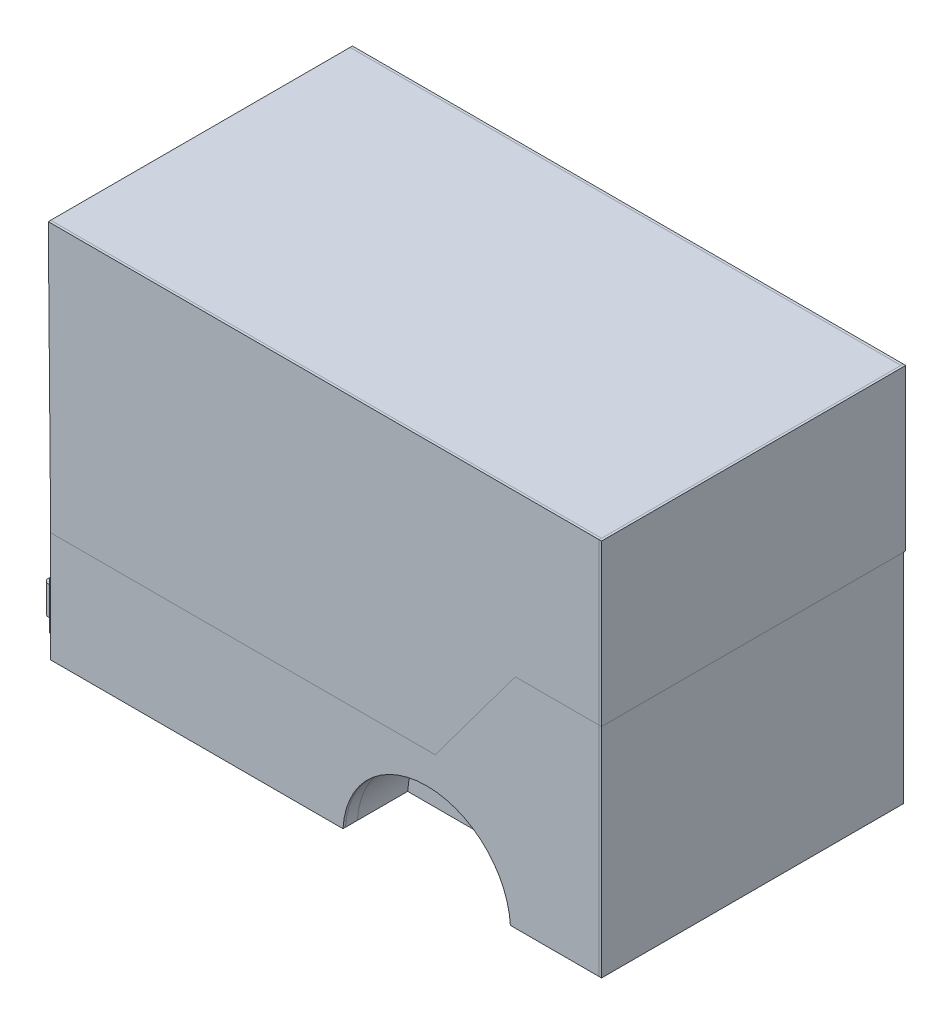
SolidWorks part; units mm, degrees
other "베이스 모듈"
other "결합장치1"
other "측벽"
other "결합장치2"
other "뒷벽인테리어(하양)"
other "뒷벽인테리어(검정)"
other "측벽인테리어(하양)2"
other "측벽인테리어(검정)2"
other "측벽인테리어(검정)1"
other "측벽인테리어(하양)1"
other "뒷벽"
other "천장"
other "뒷면벽"
other "측면벽"
ref_plane "정면" through (0, 0, 0) normal (0, 0, 1) x (1, 0, 0)
ref_plane "윗면" through (0, 0, 0) normal (0, 1, 0) x (1, 0, 0)
ref_plane "우측면" through (0, 0, 0) normal (1, 0, 0) x (0, 0, -1)
sketch "스케치1" plane through (0, 0, 0) normal (0, 1, 0) x (1, 0, 0)
  line L1 (-757.2313, -2.0205) -> (-986.2313, -2.0205)
  line L2 (-757.2313, -2.0205) -> (-757.2313, -127.0205)
  line L3 (-757.2313, -127.0205) -> (-986.2313, -127.0205)
  line L4 (-986.2313, -2.0205) -> (-986.2313, -127.0205)
extrude "보스-돌출1" add sketch "스케치1" along normal up to surface (88 mm away)
sketch "스케치4" plane through (-986.2313, 0, 0) normal (-1, 0, 0) x (0, 0, 1)
  line L4 (2.0205, 0) -> (127.0205, 0)
  line L5 (2.0205, 88) -> (2.0205, 0)
  line L6 (127.0205, 88) -> (2.0205, 88)
  line L7 (127.0205, 0) -> (127.0205, 88)
  line L8 (123.0205, 84) -> (6.0205, 84)
  line L9 (123.0205, 67.306) -> (123.0205, 84)
  line L10 (120.1014, 42.8854) -> (120.8975, 46.7066)
  line L11 (118.0205, 2) -> (118.0205, 22.694)
  line L12 (11.0205, 2) -> (118.0205, 2)
  line L13 (11.0205, 22.694) -> (11.0205, 2)
  line L14 (8.1434, 46.7066) -> (8.9395, 42.8854)
  line L15 (6.0205, 84) -> (6.0205, 67.306)
  line L16 (123.0205, 84) -> (6.0205, 84)
  line L17 (123.0205, 67.306) -> (123.0205, 84)
  line L18 (120.1014, 42.8854) -> (120.8975, 46.7066)
  line L19 (118.0205, 2) -> (118.0205, 22.694)
  line L20 (11.0205, 2) -> (118.0205, 2)
  line L21 (11.0205, 22.694) -> (11.0205, 2)
  line L22 (8.1434, 46.7066) -> (8.9395, 42.8854)
  line L23 (6.0205, 84) -> (6.0205, 67.306)
  line L24 (117.0205, 3) -> (117.0205, 22.694)
  line L25 (119.1224, 43.0894) -> (119.9185, 46.9106)
  line L26 (122.0205, 67.306) -> (122.0205, 83)
  line L27 (122.0205, 83) -> (7.0205, 83)
  line L28 (7.0205, 83) -> (7.0205, 67.306)
  line L29 (9.1224, 46.9106) -> (9.9185, 43.0894)
  line L30 (12.0205, 22.694) -> (12.0205, 3)
  line L31 (12.0205, 3) -> (117.0205, 3)
  line L32 (117.0205, 3) -> (117.0205, 22.694)
  line L33 (119.1224, 43.0894) -> (119.9185, 46.9106)
  line L34 (122.0205, 67.306) -> (122.0205, 83)
  line L35 (122.0205, 83) -> (7.0205, 83)
  line L36 (7.0205, 83) -> (7.0205, 67.306)
  line L37 (9.1224, 46.9106) -> (9.9185, 43.0894)
  line L38 (12.0205, 22.694) -> (12.0205, 3)
  line L39 (12.0205, 3) -> (117.0205, 3)
  line L40 (2.0205, 0) -> (127.0205, 0)
  line L41 (2.0205, 88) -> (2.0205, 0)
  line L42 (127.0205, 88) -> (2.0205, 88)
  line L43 (127.0205, 0) -> (127.0205, 88)
  line L44 (126.0205, 1) -> (126.0205, 87)
  line L45 (3.0205, 1) -> (126.0205, 1)
  line L46 (3.0205, 87) -> (3.0205, 1)
  line L47 (126.0205, 87) -> (3.0205, 87)
  line L48 (126.0205, 1) -> (126.0205, 87)
  line L49 (3.0205, 1) -> (126.0205, 1)
  line L50 (3.0205, 87) -> (3.0205, 1)
  line L51 (126.0205, 87) -> (3.0205, 87)
  arc A200 (120.8975, 46.7066) -> (123.0205, 67.306) centre (22.0205, 67.306) ccw
  arc A202 (120.8975, 46.7066) -> (123.0205, 67.306) centre (22.0205, 67.306) ccw
  arc A204 (120.1014, 42.8854) -> (118.0205, 22.694) centre (217.0205, 22.694) ccw
  arc A206 (120.1014, 42.8854) -> (118.0205, 22.694) centre (217.0205, 22.694) ccw
  arc A208 (11.0205, 22.694) -> (8.9395, 42.8854) centre (-87.9795, 22.694) ccw
  arc A209 (11.0205, 22.694) -> (8.9395, 42.8854) centre (-87.9795, 22.694) ccw
  arc A210 (6.0205, 67.306) -> (8.1434, 46.7066) centre (107.0205, 67.306) ccw
  arc A211 (6.0205, 67.306) -> (8.1434, 46.7066) centre (107.0205, 67.306) ccw
  arc A212 (119.1224, 43.0894) -> (117.0205, 22.694) centre (217.0205, 22.694) ccw
  arc A213 (119.1224, 43.0894) -> (117.0205, 22.694) centre (217.0205, 22.694) ccw
  arc A214 (119.9185, 46.9106) -> (122.0205, 67.306) centre (22.0205, 67.306) ccw
  arc A215 (119.9185, 46.9106) -> (122.0205, 67.306) centre (22.0205, 67.306) ccw
  arc A216 (7.0205, 67.306) -> (9.1224, 46.9106) centre (107.0205, 67.306) ccw
  arc A217 (7.0205, 67.306) -> (9.1224, 46.9106) centre (107.0205, 67.306) ccw
  arc A218 (12.0205, 22.694) -> (9.9185, 43.0894) centre (-87.9795, 22.694) ccw
  arc A219 (12.0205, 22.694) -> (9.9185, 43.0894) centre (-87.9795, 22.694) ccw
  line M33 (127.0205, 88) -> (2.0205, 88)
  line M34 (2.0205, 88) -> (2.0205, 0)
  line M35 (2.0205, 0) -> (127.0205, 0)
  line M36 (127.0205, 0) -> (127.0205, 88)
  dimension "D1" = 0
  dimension "D2" = 0
  dimension "D3" = 0
  dimension "D4" = 0
extrude "컷-돌출3" cut sketch "스케치4" against normal blind 1 contours L51 L48 L49 L50 M36 M33 M34 M35 | L23 A211 L22 A209 L21 L20 L19 A206 L18 A202 L17 L16 L38 A219 L37 A217 L36 L35 L34 A215 L33 A213 L32 L39 region at (-986.2313, 44, 2.1733) region at (-986.2313, 75.653, 122.8776)
sketch "스케치5" plane through (-757.2313, 0, 0) normal (1, 0, 0) x (0, 0, -1)
  line L4 (-2.0205, 88) -> (-127.0205, 88)
  line L5 (-127.0205, 88) -> (-127.0205, 0)
  line L6 (-127.0205, 0) -> (-2.0205, 0)
  line L7 (-2.0205, 0) -> (-2.0205, 88)
  line L8 (-2.0205, 88) -> (-127.0205, 88)
  line L9 (-127.0205, 88) -> (-127.0205, 0)
  line L10 (-127.0205, 0) -> (-2.0205, 0)
  line L11 (-2.0205, 0) -> (-2.0205, 88)
  dimension "D1" = 0
extrude "보스-돌출2" add sketch "스케치5" along normal blind 1
sketch "스케치11" plane through (-986.2313, 0, 0) normal (-1, 0, 0) x (0, 0, 1)
  line L4 (124.5205, 6) -> (124.5205, 26)
  line L5 (119.5205, 6) -> (124.5205, 6)
  line L6 (119.5205, 26) -> (119.5205, 6)
  line L7 (124.5205, 26) -> (119.5205, 26)
  line L8 (124.5205, 6) -> (124.5205, 26)
  line L9 (119.5205, 6) -> (124.5205, 6)
  line L10 (119.5205, 26) -> (119.5205, 6)
  line L11 (124.5205, 26) -> (119.5205, 26)
  dimension "D1" = 0
extrude "보스-돌출3" add sketch "스케치11" along normal blind 2 separate body
ref_plane "평면2" through (0, 23, 0) normal (0, 1, 0) x (1, 0, 0)
sketch "스케치12" plane through (0, 23, 0) normal (0, 1, 0) x (1, 0, 0)
  line L0 (-988.2313, -124.5205) -> (-986.2313, -124.5205) construction
  line L1 (-988.2313, -124.5205) -> (-988.2313, -119.5205) construction
  circle A0 centre (-989.2313, -122.0205) radius 2
  dimension "D1" = 4
  dimension "D2" = 2.5
  dimension "D3" = 1
extrude "보스-돌출4" add sketch "스케치12" against normal blind 12
ref_plane "평면3" through (0, 0, 64.5205) normal (0, 0, 1) x (1, 0, 0)
mirror "대칭 복사1" about plane through (0, 0, 64.5205) normal (0, 0, 1) of bodies 111
sketch "스케치13" plane through (0, 0, 127.0205) normal (0, 0, 1) x (1, 0, 0)
  circle A0 centre (-827.2313, -2) radius 35
  dimension "D1" = 70
extrude "컷-돌출7" cut sketch "스케치13" against normal blind 26
sketch "스케치14" plane through (0, 0, 2.0205) normal (0, 0, -1) x (-1, 0, 0)
  circle A0 centre (827.2313, -2) radius 35
  dimension "D1" = 70
extrude "컷-돌출8" cut sketch "스케치14" against normal blind 26
sketch "스케치16" plane through (0, 88, 0) normal (0, 1, 0) x (1, 0, 0)
  line L4 (-756.2313, -2.0205) -> (-985.2313, -2.0205)
  line L5 (-985.2313, -2.0205) -> (-985.2313, -127.0205)
  line L6 (-985.2313, -127.0205) -> (-756.2313, -127.0205)
  line L7 (-756.2313, -127.0205) -> (-756.2313, -2.0205)
  line L8 (-756.2313, -2.0205) -> (-985.2313, -2.0205)
  line L9 (-985.2313, -2.0205) -> (-985.2313, -127.0205)
  line L10 (-985.2313, -127.0205) -> (-756.2313, -127.0205)
  line L11 (-756.2313, -127.0205) -> (-756.2313, -2.0205)
  dimension "D1" = 0
extrude "보스-돌출6" add sketch "스케치16" along normal blind 70
shell "쉘1" thickness 5 removed face at (-756.2313, 79, 64.5205)
sketch "스케치18" plane through (-981.2313, 0, 0) normal (1, 0, 0) x (0, 0, -1)
  line L8 (-17.0205, 8) -> (-17.0205, 22.694)
  line L9 (-14.8134, 44.1092) -> (-14.0173, 47.9304)
  line L10 (-12.0205, 67.306) -> (-12.0205, 78)
  line L11 (-12.0205, 78) -> (-117.0205, 78)
  line L12 (-117.0205, 78) -> (-117.0205, 67.306)
  line L13 (-115.0236, 47.9304) -> (-114.2275, 44.1092)
  line L14 (-112.0205, 22.694) -> (-112.0205, 8)
  line L15 (-112.0205, 8) -> (-17.0205, 8)
  line L16 (-17.0205, 8) -> (-17.0205, 22.694)
  line L17 (-14.8134, 44.1092) -> (-14.0173, 47.9304)
  line L18 (-12.0205, 67.306) -> (-12.0205, 78)
  line L19 (-12.0205, 78) -> (-117.0205, 78)
  line L20 (-117.0205, 78) -> (-117.0205, 67.306)
  line L21 (-115.0236, 47.9304) -> (-114.2275, 44.1092)
  line L22 (-112.0205, 22.694) -> (-112.0205, 8)
  line L23 (-112.0205, 8) -> (-17.0205, 8)
  arc A4 (-14.8134, 44.1092) -> (-17.0205, 22.694) centre (87.9795, 22.694) ccw
  arc A5 (-14.0173, 47.9304) -> (-12.0205, 67.306) centre (-107.0205, 67.306) ccw
  arc A6 (-117.0205, 67.306) -> (-115.0236, 47.9304) centre (-22.0205, 67.306) ccw
  arc A7 (-112.0205, 22.694) -> (-114.2275, 44.1092) centre (-217.0205, 22.694) ccw
  arc A8 (-14.8134, 44.1092) -> (-17.0205, 22.694) centre (87.9795, 22.694) ccw
  arc A9 (-14.0173, 47.9304) -> (-12.0205, 67.306) centre (-107.0205, 67.306) ccw
  arc A10 (-117.0205, 67.306) -> (-115.0236, 47.9304) centre (-22.0205, 67.306) ccw
  arc A11 (-112.0205, 22.694) -> (-114.2275, 44.1092) centre (-217.0205, 22.694) ccw
  dimension "D1" = 0
extrude "컷-돌출9" cut sketch "스케치18" against normal blind 70
sketch "스케치20" plane through (-756.2313, 0, 0) normal (1, 0, 0) x (0, 0, -1)
  line L4 (-127.0205, 0) -> (-2.0205, 0)
  line L5 (-2.0205, 0) -> (-2.0205, 158)
  line L6 (-2.0205, 158) -> (-127.0205, 158)
  line L7 (-127.0205, 158) -> (-127.0205, 0)
  line L8 (-127.0205, 0) -> (-2.0205, 0)
  line L9 (-2.0205, 0) -> (-2.0205, 158)
  line L10 (-2.0205, 158) -> (-127.0205, 158)
  line L11 (-127.0205, 158) -> (-127.0205, 0)
  line L12 (-122.0205, 153) -> (-122.0205, 5)
  line L13 (-122.0205, 5) -> (-7.0205, 5)
  line L14 (-7.0205, 5) -> (-7.0205, 153)
  line L15 (-7.0205, 153) -> (-122.0205, 153)
  line L16 (-122.0205, 153) -> (-122.0205, 5)
  line L17 (-122.0205, 5) -> (-7.0205, 5)
  line L18 (-7.0205, 5) -> (-7.0205, 153)
  line L19 (-7.0205, 153) -> (-122.0205, 153)
  dimension "D1" = 0
  dimension "D2" = 0
extrude "보스-돌출7" add sketch "스케치20" along normal blind 1
sketch "스케치24" plane through (0, 0, 127.0205) normal (0, 0, 1) x (1, 0, 0)
  line L0 (-755.2313, 158) -> (-755.2313, 0) construction
  line L1 (-755.2313, 153) -> (-980.2313, 153)
  line L2 (-755.2313, 153) -> (-755.2313, 5)
  line L3 (-755.2313, 5) -> (-787.8486, 5)
  line L4 (-980.2313, 153) -> (-980.2313, 5)
  line L5 (-985.2313, 158) -> (-755.2313, 158) construction
  line L6 (-792.2885, 0) -> (-755.2313, 0) construction
  line L7 (-985.2313, 0) -> (-985.2313, 158) construction
  line L8 (-866.6141, 5) -> (-980.2313, 5)
  arc A0 (-787.8486, 5) -> (-866.6141, 5) centre (-827.2313, -2) ccw
  arc M2 (-862.1741, 0) -> (-792.2885, 0) centre (-827.2313, -2) cw
  line M4 (-755.2313, 0) -> (-755.2313, 158)
  dimension "D4" = 80
  dimension "D1" = 5
  dimension "D2" = 5
  dimension "D3" = 5
extrude "컷-돌출14" cut sketch "스케치24" against normal up to surface (5 mm away) contours L8 L3 L1 L4 M2 M4 region at (-870.2589, 82.756, 127.0205)
sketch "스케치25" plane through (0, 0, 127.0205) normal (0, 0, 1) x (1, 0, 0)
  line L0 (-857.2313, -2) -> (-796.7667, -2) construction
  line L1 (-980.2313, 153) -> (-755.2313, 153)
  line L2 (-980.2313, 153) -> (-980.2313, 5)
  line L3 (-980.2313, 5) -> (-866.3818, 5)
  line L4 (-755.2313, 153) -> (-755.2313, 5)
  line L5 (-787.6163, 5) -> (-755.2313, 5)
  arc A0 (-787.6163, 5) -> (-866.3818, 5) centre (-826.999, -2) ccw
  dimension "D1" = 80
extrude "보스-돌출8" add sketch "스케치25" against normal blind 5 separate body
sketch "스케치26" plane through (0, 158, 0) normal (0, 1, 0) x (1, 0, 0)
  line L1 (-985.2313, -2.0205) -> (-755.2313, -2.0205)
  line L2 (-985.2313, -2.0205) -> (-985.2313, -127.0205)
  line L3 (-985.2313, -127.0205) -> (-755.2313, -127.0205)
  line L4 (-755.2313, -2.0205) -> (-755.2313, -127.0205)
extrude "컷-돌출15" cut sketch "스케치26" against normal blind 5
sketch "스케치27" plane through (0, 153, 0) normal (0, 1, 0) x (1, 0, 0)
  line L1 (-985.2313, -2.0205) -> (-755.2313, -2.0205)
  line L2 (-985.2313, -2.0205) -> (-985.2313, -127.0205)
  line L3 (-985.2313, -127.0205) -> (-755.2313, -127.0205)
  line L4 (-755.2313, -2.0205) -> (-755.2313, -127.0205)
extrude "보스-돌출9" add sketch "스케치27" along normal blind 5 separate body
sketch "스케치28" plane through (0, 5, 0) normal (0, 1, 0) x (1, 0, 0)
  line L1 (-755.2313, -7.0205) -> (-760.2313, -7.0205)
  line L2 (-755.2313, -7.0205) -> (-755.2313, -122.0205)
  line L3 (-755.2313, -122.0205) -> (-760.2313, -122.0205)
  line L4 (-760.2313, -7.0205) -> (-760.2313, -122.0205)
  dimension "D1" = 5
extrude "보스-돌출10" add sketch "스케치28" along normal up to surface (148 mm away) separate body up to face at (-870.2313, 153, 64.5205)
sketch "스케치29" plane through (0, 0, 2.0205) normal (0, 0, -1) x (-1, 0, 0)
  line L0 (984.2313, 0) -> (984.2313, 88) construction
  line L1 (984.2313, 46) -> (823.6551, 46)
  line L2 (984.2313, 46) -> (984.2313, 0)
  line L3 (984.2313, 0) -> (862.1741, 0)
  line L5 (792.2885, 0) -> (755.2313, 0)
  line L6 (755.2313, 90.9094) -> (790.2313, 90.9094)
  line L7 (755.2313, 0) -> (755.2313, 153) construction
  line L8 (790.2313, 90.9094) -> (823.6551, 46)
  line L9 (755.2313, 90.9094) -> (755.2313, 0)
  arc A0 (862.1741, 0) -> (792.2885, 0) centre (827.2313, -2) ccw
  line M6 (755.2313, 153) -> (755.2313, 0)
  line M7 (755.2313, 0) -> (792.2885, 0)
  arc M8 (792.2885, 0) -> (862.1741, 0) centre (827.2313, -2) cw
  line M9 (862.1741, 0) -> (985.2313, 0)
  dimension "D1" = 35
extrude "보스-돌출11" add sketch "스케치29" along normal blind 1 separate body contours L8 L6 L2 L1 M6 M7 M8 M9 region at (-858.1762, 33.4866, 2.0205)
sketch "스케치30" plane through (0, 0, 2.0205) normal (0, 0, -1) x (-1, 0, 0)
  line L0 (755.2313, 90.9094) -> (755.2313, 158)
  line L1 (755.2313, 158) -> (985.2313, 158)
  line L2 (985.2313, 158) -> (984.2313, 46)
  line L3 (984.2313, 46) -> (823.6551, 46)
  line L4 (984.2313, 46) -> (823.6551, 46) construction
  line L5 (823.6551, 46) -> (790.2313, 90.9094)
  line L6 (790.2313, 90.9094) -> (755.2313, 90.9094)
extrude "보스-돌출12" add sketch "스케치30" along normal blind 1 separate body
delete or keep bodies "바디-삭제/보존 2" type delete bodies bodies 112
ref_plane "평면5" through (0, 0, 64.5205) normal (0, 0, 1) x (1, 0, 0)
mirror "대칭 복사3" about plane through (0, 0, 64.5205) normal (0, 0, 1) of bodies 131 130
sketch "스케치32" plane through (-755.2313, 0, 0) normal (1, 0, 0) x (0, 0, -1)
  line L1 (-128.0205, 90.9094) -> (-1.0205, 90.9094)
  line L2 (-128.0205, 90.9094) -> (-128.0205, 158)
  line L3 (-128.0205, 158) -> (-1.0205, 158)
  line L4 (-1.0205, 90.9094) -> (-1.0205, 158)
extrude "보스-돌출13" add sketch "스케치32" along normal blind 1 separate body
sketch "스케치33" plane through (-755.2313, 0, 0) normal (1, 0, 0) x (0, 0, -1)
  line L1 (-128.0205, 90.9094) -> (-2.0205, 90.9094)
  line L2 (-128.0205, 90.9094) -> (-128.0205, 0)
  line L3 (-128.0205, 0) -> (-2.0205, 0)
  line L4 (-2.0205, 90.9094) -> (-2.0205, 0)
extrude "보스-돌출14" add sketch "스케치33" along normal blind 1 separate body
mirror "대칭 복사4" about plane through (0, 0, 64.5205) normal (0, 0, 1) of bodies 111
delete or keep bodies "바디-삭제/보존 3" type delete bodies bodies 126
sketch "스케치34" plane through (0, 5, 0) normal (0, 1, 0) x (1, 0, 0)
  line L1 (-980.2313, -127.0205) -> (-755.2313, -127.0205)
  line L2 (-980.2313, -127.0205) -> (-980.2313, -122.0205)
  line L3 (-980.2313, -122.0205) -> (-755.2313, -122.0205)
  line L4 (-755.2313, -127.0205) -> (-755.2313, -122.0205)
extrude "컷-돌출16" cut sketch "스케치34" against normal blind 10 and the other way blind 40
sketch "스케치35" plane through (0, 0, 122.0205) normal (0, 0, 1) x (1, 0, 0)
  line L0 (-980.2313, 0) -> (-760.2313, 0)
  line L2 (-980.2313, 0) -> (-980.2313, 153)
  line L3 (-980.2313, 153) -> (-760.2313, 153)
  line L4 (-760.2313, 0) -> (-760.2313, 153)
extrude "보스-돌출16" add sketch "스케치35" along normal blind 5 separate body
sketch "스케치36" plane through (-760.2313, 0, 0) normal (1, 0, 0) x (0, 0, -1)
  line L4 (-122.0205, 0) -> (-122.0205, 153)
  line L5 (-122.0205, 153) -> (-127.0205, 153)
  line L6 (-127.0205, 153) -> (-127.0205, 0)
  line L7 (-127.0205, 0) -> (-122.0205, 0)
  line L8 (-122.0205, 0) -> (-122.0205, 153)
  line L9 (-122.0205, 153) -> (-127.0205, 153)
  line L10 (-127.0205, 153) -> (-127.0205, 0)
  line L11 (-127.0205, 0) -> (-122.0205, 0)
  dimension "D1" = 0
extrude "보스-돌출17" add sketch "스케치36" along normal up to surface (5 mm away) up to face at (-755.2313, 124.4547, 64.5205)
sketch "스케치37" plane through (0, 0, 127.0205) normal (0, 0, 1) x (1, 0, 0)
  line L1 (-862.1741, 0) -> (-792.2885, 0)
  line L2 (-862.1741, 0) -> (-792.2885, 0)
  arc A1 (-792.2885, 0) -> (-862.1741, 0) centre (-827.2313, -2) ccw
  arc A2 (-792.2885, 0) -> (-862.1741, 0) centre (-827.2313, -2) ccw
  dimension "D1" = 0
extrude "컷-돌출17" cut sketch "스케치37" against normal blind 5
delete or keep bodies "바디-삭제/보존 4" type delete bodies bodies 129
sketch "스케치39" plane through (-755.2313, 0, 0) normal (1, 0, 0) x (0, 0, -1)
  line L0 (-122.0205, 5) -> (-122.0205, 0) construction
  line L1 (-7.0205, 5) -> (-122.0205, 5)
  line L2 (-7.0205, 5) -> (-7.0205, 0)
  line L3 (-7.0205, 0) -> (-122.0205, 0)
  line L4 (-122.0205, 5) -> (-122.0205, 0)
  line L5 (-122.0205, 0) -> (-2.0205, 0) construction
extrude "컷-돌출18" cut sketch "스케치39" against normal blind 5
sketch "스케치40" plane through (0, 0, 0) normal (0, -1, 0) x (1, 0, 0)
  line L1 (-760.2313, 7.0205) -> (-755.2313, 7.0205)
  line L2 (-760.2313, 7.0205) -> (-760.2313, 127.0205)
  line L3 (-760.2313, 127.0205) -> (-755.2313, 127.0205)
  line L4 (-755.2313, 7.0205) -> (-755.2313, 127.0205)
  dimension "D1" = 120
extrude "보스-돌출19" add sketch "스케치40" against normal up to surface (153 mm away) separate body up to face at (-870.2313, 153, 64.5205)
sketch "스케치45" plane through (0, 5, 0) normal (0, 1, 0) x (1, 0, 0)
  line L1 (-866.6141, -7.0205) -> (-787.8486, -7.0205)
  line L2 (-866.6141, -7.0205) -> (-866.6141, -33.0205)
  line L3 (-866.6141, -33.0205) -> (-787.8486, -33.0205)
  line L4 (-787.8486, -7.0205) -> (-787.8486, -33.0205)
  line L5 (-866.6141, -122.0205) -> (-787.8486, -122.0205)
  line L6 (-866.6141, -122.0205) -> (-866.6141, -96.0205)
  line L7 (-866.6141, -96.0205) -> (-787.8486, -96.0205)
  line L8 (-787.8486, -122.0205) -> (-787.8486, -96.0205)
extrude "보스-돌출21" add sketch "스케치45" along normal blind 33
sketch "스케치47" plane through (0, 0, 122.0205) normal (0, 0, 1) x (1, 0, 0)
  line L0 (-862.1741, 0) -> (-792.2885, 0) construction
  line L1 (-862.1741, 0) -> (-792.2885, 0)
  arc A0 (-792.2885, 0) -> (-862.1741, 0) centre (-827.2313, -2) ccw construction
  arc A1 (-792.2885, 0) -> (-862.1741, 0) centre (-827.2313, -2) ccw
extrude "컷-돌출20" cut sketch "스케치47" against normal blind 21
sketch "스케치48" plane through (0, 0, 7.0205) normal (0, 0, -1) x (-1, 0, 0)
  circle A0 centre (827.2523, -1.9146) radius 34.912
extrude "컷-돌출21" cut sketch "스케치48" against normal blind 21
